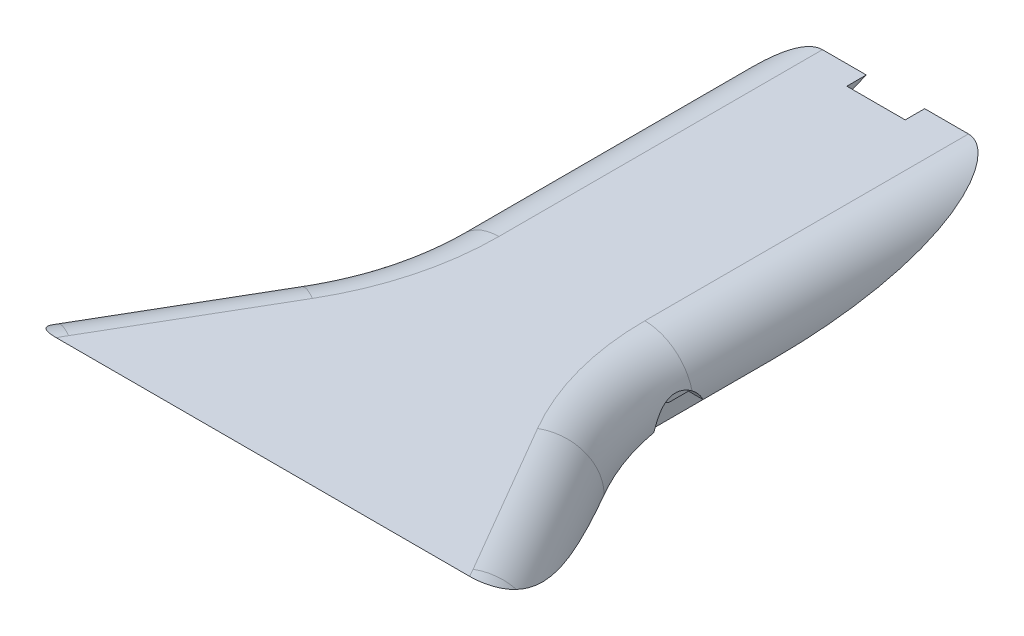
SolidWorks part; units mm, degrees
ref_plane "Спереди" through (0, 0, 0) normal (0, 0, 1) x (1, 0, 0)
ref_plane "Сверху" through (0, 0, 0) normal (0, 1, 0) x (1, 0, 0)
ref_plane "Справа" through (0, 0, 0) normal (1, 0, 0) x (0, 0, -1)
sketch "Эскиз1" plane through (0, 0, 0) normal (0, 1, 0) x (1, 0, 0)
  line L1 (21, 25) -> (-21, 25)
  line L2 (-21, 25) -> (-21, 0)
  line L3 (-21, 0) -> (-28.5, 0)
  line L4 (-28.5, 0) -> (-28.5, 35)
  line L5 (-28.5, 35) -> (-12.5, 62.5)
  line L6 (-12.5, 62.5) -> (-12.5, 110)
  line L7 (-12.5, 110) -> (12.5, 110)
  line L12 (0, -1000) -> (0, 49000) construction
  line L13 (12.5, 62.5) -> (12.5, 110)
  line L14 (28.5, 35) -> (12.5, 62.5)
  line L15 (28.5, 0) -> (28.5, 35)
  line L16 (21, 0) -> (28.5, 0)
  line L17 (21, 25) -> (21, 0)
  point P13 (-24.75, 0)
  point P15 (0, 110)
  point P16 (0, 25)
  dimension "D1" = 21
  dimension "D2" = 7.5
  dimension "D3" = 25
  dimension "D4" = 10
  dimension "D5" = 110
  dimension "D6" = 12.5
  dimension "D7" = 47.5
extrude "Бобышка-Вытянуть1" add sketch "Эскиз1" along normal blind 20
sketch "Эскиз2" plane through (28.5, 0, 0) normal (1, 0, 0) x (0, 0, -1)
  line L0 (-1000, 10) -> (49000, 10) construction
  line L1 (0, 20) -> (0, 0) construction
  line L2 (10, -980) -> (10, 49020) construction
  circle A0 centre (10, 10) radius 4
  point P5 (0, 10)
  dimension "D1" = 8
  dimension "D2" = 10
extrude "Вырез-Вытянуть1" cut sketch "Эскиз2" against normal blind 52
fillet "Скругление1" radius 25 4 edges at (-28.5, 10, -35) (-12.5, 10, -62.5) (28.5, 10, -35) (12.5, 10, -62.5)
fillet "Скругление2" radius 5 26 edges at (-28.5, 20, -14.1282) (-27.6373, 20, -34.7673) (-20.5, 20, -48.75) (-13.3627, 20, -62.7327) (-28.5, 0, -14.1282) (-27.6373, 0, -34.7673) (-20.5, 0, -48.75) (-13.3627, 0, -62.7327) (28.5, 0, -14.1282) (27.6373, 0, -34.7673) (20.5, 0, -48.75) (13.3627, 0, -62.7327) (28.5, 20, -14.1282) (27.6373, 20, -34.7673) (20.5, 20, -48.75) (13.3627, 20, -62.7327) (-24.75, 0, 0) (-24.75, 20, 0) (-28.5, 10, 0) (-12.5, 20, -89.6218) (-12.5, 0, -89.6218) (28.5, 10, 0) (24.75, 0, 0) (24.75, 20, 0) (12.5, 0, -89.6218) (12.5, 20, -89.6218)
fillet "Скругление3" radius 10 2 edges at (0, 0, -25) (0, 20, -25)
sketch "Эскиз4" plane through (28.5, 0, 0) normal (1, 0, 0) x (0, 0, -1)
  line L1 (6, 6) -> (14, 6)
  line L2 (6, 6) -> (6, 14)
  line L3 (6, 14) -> (14, 14)
  line L4 (14, 6) -> (14, 14)
  line L5 (6, 6) -> (14, 14) construction
  line L6 (6, 14) -> (14, 6) construction
  point P0 (10, 10)
  dimension "D1" = 8
extrude "Вырез-Вытянуть2" cut sketch "Эскиз4" against normal blind 5
extrude "Вырез-Вытянуть3" cut sketch "Эскиз4<2>" along normal blind 5 from vertex starting at point (-28.5, 5, -5)
sketch "Эскиз4<2>" plane through (28.5, 0, 0) normal (1, 0, 0) x (0, 0, -1) same geometry as "Эскиз4"
sketch "Эскиз5" plane through (0, 0, -110) normal (0, 0, -1) x (-1, 0, 0)
  line L1 (-7.5, 20) -> (7.5, 20)
  line L2 (-7.5, 20) -> (-7.5, 15)
  line L3 (-7.5, 15) -> (7.5, 15)
  line L4 (7.5, 20) -> (7.5, 15)
  line L5 (-7.5, 0) -> (7.5, 0)
  line L6 (-7.5, 0) -> (-7.5, 5)
  line L7 (-7.5, 5) -> (7.5, 5)
  line L8 (7.5, 0) -> (7.5, 5)
  dimension "D1" = 5
  dimension "D2" = 5
extrude "Вырез-Вытянуть4" cut sketch "Эскиз5" against normal blind 7.5
sketch "Эскиз6" plane through (0, 15, 0) normal (0, 1, 0) x (1, 0, 0)
  line L0 (-1007.5, 106.25) -> (48992.5, 106.25) construction
  line L1 (-7.5, 102.5) -> (-7.5, 110) construction
  line L2 (0, -880) -> (0, 49120) construction
  line L3 (7.5, 110) -> (-7.5, 110) construction
  circle A0 centre (-4, 106.25) radius 1.45
  circle A1 centre (4, 106.25) radius 1.45
  point P5 (-7.5, 106.25)
  point P10 (0, 110)
  dimension "D1" = 2.9
  dimension "D2" = 4
extrude "Вырез-Вытянуть5" cut sketch "Эскиз6" against normal blind 10
sketch "Эскиз8" plane through (0, 0, 0) normal (1, 0, 0) x (0, 0, -1)
  line L0 (110, 15) -> (110, 5) construction
  line L1 (102.5, 18) -> (37.5, 18)
  line L2 (102.5, 18) -> (102.5, 2)
  line L3 (102.5, 2) -> (37.5, 2)
  line L5 (69.2436, 20) -> (102.5, 20) construction
  line L6 (102.5, 0) -> (69.2436, 0) construction
  arc A0 (37.5, 2) -> (37.5, 18) centre (37.5, 10) cw
  dimension "D1" = 7.5
  dimension "D2" = 2
  dimension "D3" = 2
  dimension "D4" = 65
extrude "Вырез-Вытянуть6" cut sketch "Эскиз8" against normal mid plane 14
sketch "Эскиз9" plane through (0, 0, -110) normal (0, 0, -1) x (-1, 0, 0)
  line L0 (-1012.5, 10) -> (48987.5, 10) construction
  line L1 (-12.5, 15) -> (-12.5, 5) construction
  line L2 (-10, -990) -> (-10, 49010) construction
  line L3 (10, -990) -> (10, 49010) construction
  line L4 (-12.5, 15) -> (-12.5, 5) construction
  line L5 (12.5, 5) -> (12.5, 15) construction
  circle A0 centre (-10, 10) radius 1.45
  circle A1 centre (10, 10) radius 1.45
  point P5 (-12.5, 10)
  dimension "D3" = 2.9
  dimension "D1" = 2.5
  dimension "D2" = 2.5
extrude "Вырез-Вытянуть7" cut sketch "Эскиз9" against normal blind 90
sketch "Эскиз10" plane through (0, 0, 0) normal (1, 0, 0) x (0, 0, -1)
  line L0 (102.5, 20) -> (110, 20) construction
  line L1 (69.2436, 20) -> (102.5, 20) construction
  line L2 (110, 15) -> (69.2436, 15) construction
  line L3 (38.3143, 20) -> (54.1567, 20) construction
  line L4 (56.6712, 15) -> (40.8288, 15) construction
  line L5 (37.5, 20) -> (102.5, 20)
  line L6 (77.5, 15) -> (57.5, 15)
  line L7 (110, 15) -> (110, 5) construction
  line L9 (-6.9324, 29.6896) -> (129.9803, 29.6896)
  line L10 (-6.9324, 29.6896) -> (-6.9324, -7.3732)
  line L11 (-6.9324, -7.3732) -> (129.9803, -7.3732)
  line L12 (129.9803, 29.6896) -> (129.9803, -7.3732)
  arc A0 (102.5, 20) -> (77.5, 15) centre (77.5, 80) cw
  arc A1 (37.5, 20) -> (57.5, 15) centre (57.5, 57.5) ccw
  dimension "D1" = 7.5
  dimension "D4" = 25
  dimension "D2" = 65
  dimension "D3" = 20
extrude "Вырез-Вытянуть8" cut sketch "Эскиз10" against normal through all both and the other way through all
sketch "Эскиз11" plane through (0, 15, 0) normal (0, -1, 0) x (1, 0, 0)
  line L1 (7, -57.5) -> (9.5, -57.5)
  line L2 (7, -57.5) -> (7, -77.5)
  line L3 (7, -77.5) -> (9.5, -77.5)
  line L4 (9.5, -57.5) -> (9.5, -77.5)
  line L6 (-7, -57.5) -> (-9.5, -57.5)
  line L7 (-7, -57.5) -> (-7, -77.5)
  line L8 (-7, -77.5) -> (-9.5, -77.5)
  line L9 (-9.5, -57.5) -> (-9.5, -77.5)
  line L11 (-12.5, -77.5) -> (-7, -77.5) construction
  line L13 (7, -77.5) -> (12.5, -77.5) construction
  dimension "D1" = 2.5
extrude "Бобышка-Вытянуть2" add sketch "Эскиз11" along normal blind 3
sketch "Эскиз12" plane through (9.5, 0, 0) normal (1, 0, 0) x (0, 0, -1)
  line L0 (-942.5, 13.75) -> (49057.5, 13.75) construction
  line L3 (77.5, 12) -> (57.5, 12) construction
  circle A0 centre (67.5, 13.75) radius 1.45
  point P10 (67.5, 12)
  dimension "D1" = 2.9
  dimension "D2" = 1.75
extrude "Вырез-Вытянуть9" cut sketch "Эскиз12" against normal through all both and the other way through all
sketch "Эскиз13" plane through (9.5, 0, 0) normal (1, 0, 0) x (0, 0, -1)
  circle A0 centre (67.5, 13.75) radius 3
  arc A1 (66.7652, 15) -> (68.2348, 15) centre (67.5, 13.75) ccw construction
  dimension "D1" = 6
extrude "Вырез-Вытянуть10" cut sketch "Эскиз13" against normal blind 1.5 and the other way through all from vertex starting at point (12.5, 15, -69.2436)
extrude "Вырез-Вытянуть11" cut sketch "Эскиз13<2>" along normal blind 1.5 and the other way through all from vertex starting at point (-12.5, 15, -69.2436)
sketch "Эскиз13<2>" plane through (9.5, 0, 0) normal (1, 0, 0) x (0, 0, -1) same geometry as "Эскиз13"
sketch "Эскиз14" plane through (0, 20, 0) normal (0, 1, 0) x (1, 0, 0)
  line L0 (-7.5, 102.5) -> (7.5, 102.5) construction
  line L1 (-3, 102.5) -> (3, 102.5)
  line L2 (-3, 102.5) -> (-3, 100.5)
  line L3 (-3, 100.5) -> (3, 100.5)
  line L4 (3, 102.5) -> (3, 100.5)
  point P6 (0, 102.5)
  dimension "D1" = 2
  dimension "D2" = 6
extrude "Вырез-Вытянуть12" cut sketch "Эскиз14" against normal blind 1.5
